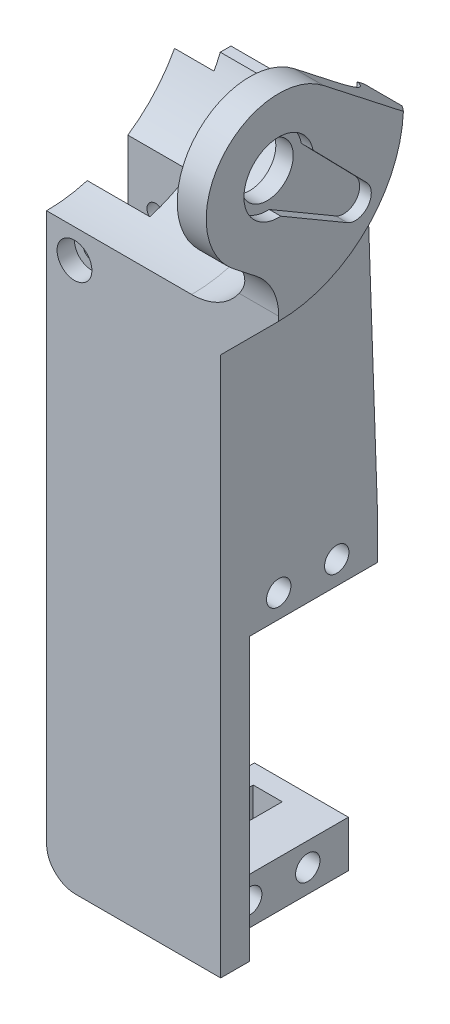
SolidWorks part; units mm, degrees
ref_plane "Alzado" through (0, 0, 0) normal (0, 0, 1) x (1, 0, 0)
ref_plane "Planta" through (0, 0, 0) normal (0, 1, 0) x (1, 0, 0)
ref_plane "Vista lateral" through (0, 0, 0) normal (1, 0, 0) x (0, 0, -1)
sketch "Croquis1" plane through (0, 0, 0) normal (0, 1, 0) x (1, 0, 0)
  line L1 (-15, -13.5) -> (15, -13.5)
  line L2 (-15, -13.5) -> (-15, 13.5)
  line L3 (-15, 13.5) -> (15, 13.5)
  line L4 (15, -13.5) -> (15, 13.5)
  line L5 (-15, -13.5) -> (15, 13.5) construction
  line L6 (-15, 13.5) -> (15, -13.5) construction
  point P0 (0, 0)
  dimension "D1" = 30
  dimension "D2" = 27
extrude "Saliente-Extruir1" add sketch "Croquis1" along normal blind 58.5 and the other way blind 56.5
sketch "Croquis17" plane through (0, 0, -13.5) normal (0, 0, -1) x (-1, 0, 0)
  line L1 (15, -48.5) -> (-15, -48.5)
  line L2 (15, -48.5) -> (15, -8)
  line L3 (15, -8) -> (-15, -8)
  line L4 (-15, -48.5) -> (-15, -8)
  line L5 (-15, -56.5) -> (-15, 58.5) construction
  line L6 (15, -56.5) -> (15, 58.5) construction
  dimension "D1" = 40.5
  dimension "D2" = 8
sketch "Croquis3" plane through (15, 0, 0) normal (1, 0, 0) x (0, 0, -1)
  line L0 (13.5, 0) -> (-13.5, 0) construction
  line L2 (-13.5, -56.5) -> (-13.5, 58.5) construction
  circle A0 centre (-13.5, 68) radius 31.5
  dimension "D1" = 63
  dimension "D2" = 68
extrude "Cortar-Extruir15" cut sketch "Croquis17" against normal blind 22
extrude "Saliente-Extruir2" add sketch "Croquis3" along normal blind 10
sketch "Croquis6" plane through (-15, 0, 0) normal (-1, 0, 0) x (0, 0, 1)
  line L0 (-13.5, 58.5) -> (13.5, 58.5) construction
  line L1 (-0.5, 58.5) -> (6.5, 58.5)
  line L2 (-0.5, 58.5) -> (-0.5, 33)
  line L3 (-0.5, 33) -> (6.5, 33)
  line L4 (6.5, 58.5) -> (6.5, 33)
  line L5 (13.5, -56.5) -> (13.5, 58.5) construction
  line L6 (22, 0) -> (-22, 0) construction
  dimension "D1" = 7
  dimension "D2" = 7
  dimension "D3" = 33
extrude "Cortar-Extruir5" cut sketch "Croquis6" against normal blind 10.8
sketch "Croquis8" plane through (15, 0, 0) normal (-1, 0, 0) x (0, 0, 1)
  line L2 (-11.2567, 64.5207) -> (-13.5, 0)
  line L5 (-13.5, -8) -> (-13.5, 51.775) construction
  line L8 (-11.2567, 64.5207) -> (5.8042, 77.8501)
  line L9 (21.1958, 58.1499) -> (13.5, 52.1373)
  line L10 (13.5, 36.5) -> (13.5, 58.5) construction
  line L11 (13.5, 52.1373) -> (13.5, 36.5)
  line L12 (21.725, 0) -> (-21.725, 0) construction
  line L13 (-13.5, 0) -> (-13.5, 51.775)
  arc A3 (21.1958, 58.1499) -> (5.8042, 77.8501) centre (13.5, 68) ccw
  circle A5 centre (13.5, 68) radius 25 construction
  arc A7 (13.5, 36.5) -> (-13.5, 51.775) centre (13.5, 68) ccw
  dimension "D1" = 25
  dimension "D2" = 128
  dimension "D5" = 50
  dimension "D3" = 31.5
extrude "Cortar-Extruir6" cut sketch "Croquis8" against normal through all and the other way up to surface (30 mm away) other way up to face at (-15, 6.1667, 0.1667)
sketch "Croquis5" plane through (-15, 0, 0) normal (-1, 0, 0) x (0, 0, 1)
  line L0 (-13.5, 0) -> (-11.466, 58.5)
  line L1 (-11.466, 58.5) -> (-8.4642, 58.5)
  line L2 (6.5, 58.5) -> (13.5, 58.5) construction
  line L3 (-8.4642, 58.5) -> (-10.4982, 0)
  line L4 (-10.4982, 0) -> (-13.5, 0)
  line L5 (21.725, 0) -> (-21.725, 0) construction
  line L6 (-13.5, 0) -> (-11.466, 58.5) construction
  dimension "D1" = 3
extrude "Cortar-Extruir4" cut sketch "Croquis5" against normal blind 6.8
sketch "Croquis9" plane through (-15, 0, 0) normal (-1, 0, 0) x (0, 0, 1)
  circle A0 centre (13.5, 68) radius 25
  dimension "D1" = 50
extrude "Cortar-Extruir7" cut sketch "Croquis9" against normal blind 35
sketch "Croquis10" plane through (25, 0, 0) normal (1, 0, 0) x (0, 0, -1)
  line L0 (-13.5, 68) -> (-0.3008, 57.6877) construction
  line L1 (11.2567, 64.5207) -> (-5.8042, 77.8501) construction
  line L2 (-13.1432, 62.0106) -> (-7.6022, 69.1027) construction
  line L3 (-7.6022, 69.1027) -> (1.6669, 59.6088)
  line L4 (-13.1432, 62.0106) -> (-1.6888, 55.3137)
  arc A0 (-7.6022, 69.1027) -> (-13.1432, 62.0106) centre (-13.5, 68) ccw
  arc A3 (-1.6888, 55.3137) -> (1.6669, 59.6088) centre (-0.3008, 57.6877) ccw
  point P10 (-10.3727, 65.5567)
  dimension "D1" = 12
  dimension "D3" = 5.5
  dimension "D2" = 16.75
  dimension "D4" = 9
extrude "Cortar-Extruir8" cut sketch "Croquis10" against normal blind 2 contours A0 region at (25, 64.7957, 9.3987)
sketch "Croquis12" plane through (0, 0, 13.5) normal (0, 0, 1) x (1, 0, 0)
  line L0 (-15, 38) -> (-10.2, 38) construction
  line L1 (-15, -56.5) -> (-15, 43) construction
  circle A0 centre (-10.2, 38) radius 3
  dimension "D3" = 6
  dimension "D1" = 4.8
  dimension "D2" = 5
extrude "Cortar-Extruir10" cut sketch "Croquis12" against normal blind 3 contours A0
sketch "Croquis13" plane through (0, 0, 10.5) normal (0, 0, 1) x (1, 0, 0)
  circle A0 centre (-10.2, 38) radius 1.5
  dimension "D1" = 3
extrude "Cortar-Extruir11" cut sketch "Croquis13" against normal through all
sketch "Croquis15" plane through (0, -56.5, 0) normal (0, -1, 0) x (1, 0, 0)
  line L0 (-0.5, 3.5) -> (-0.5, 13.5) construction
  line L2 (-0.5, -6.5) -> (-0.5, 3.5) construction
  line L3 (-15, 13.5) -> (15, 13.5) construction
  line L4 (2, -10.1) -> (-3, -10.1)
  line L5 (2, -10.1) -> (2, -2.9)
  line L6 (2, -2.9) -> (-3, -2.9)
  line L7 (-3, -10.1) -> (-3, -2.9)
  line L8 (2, -10.1) -> (-3, -2.9) construction
  line L9 (2, -2.9) -> (-3, -10.1) construction
  line L10 (2, -0.1) -> (-3, -0.1)
  line L11 (2, -0.1) -> (2, 7.1)
  line L12 (2, 7.1) -> (-3, 7.1)
  line L13 (-3, -0.1) -> (-3, 7.1)
  line L14 (2, -0.1) -> (-3, 7.1) construction
  line L15 (2, 7.1) -> (-3, -0.1) construction
  point P0 (0, 13.5)
  dimension "D1" = 10
  dimension "D2" = 0.5
  dimension "D3" = 10
  dimension "D4" = 7.2
  dimension "D5" = 5
extrude "Cortar-Extruir13" cut sketch "Croquis15" against normal up to vertex (56.5 mm away) up to point (-15, 0, -13.5)
sketch "Croquis19" plane through (15, 0, 0) normal (1, 0, 0) x (0, 0, -1)
  line L0 (-13.5, -52.5) -> (-3.5, -52.5) construction
  line L1 (-13.5, -56.5) -> (-13.5, 36.5) construction
  line L2 (13.5, -56.5) -> (13.5, -48.5) construction
  line L3 (-8.5, -28.25) -> (-13.5, -28.25) construction
  line L4 (-8.5, -8) -> (-8.5, -48.5) construction
  circle A0 centre (-3.5, -52.5) radius 2.1
  circle A1 centre (6.5, -52.5) radius 2.1
  circle A2 centre (6.5, -4) radius 2.1
  circle A3 centre (-3.5, -4) radius 2.1
  point P7 (13.5, -52.5)
  dimension "D2" = 4.2
  dimension "D1" = 10
  dimension "D3" = 10
extrude "Cortar-Extruir17" cut sketch "Croquis19" against normal blind 13
sketch "Croquis11" plane through (23, 0, 0) normal (1, 0, 0) x (0, 0, -1)
  circle A0 centre (-13.5, 68) radius 4.5
  dimension "D1" = 9
extrude "Cortar-Extruir9" cut sketch "Croquis11" against normal up to surface (3 mm away) up to face at (20, 59.7451, 9.7141)
sketch "Croquis20" plane through (0, -48.5, 0) normal (0, 1, 0) x (1, 0, 0)
  line L0 (15, -8.5) -> (-15, -8.5) construction
  line L1 (15, 13.5) -> (10, 13.5)
  line L2 (15, 13.5) -> (15, -8.5)
  line L3 (15, -8.5) -> (10, -8.5)
  line L4 (10, 13.5) -> (10, -8.5)
  line L6 (-15, 13.5) -> (-6.2, 13.5)
  line L7 (-15, 13.5) -> (-15, -8.5)
  line L8 (-15, -8.5) -> (-6.2, -8.5)
  line L9 (-6.2, 13.5) -> (-6.2, -8.5)
  dimension "D1" = 5
  dimension "D2" = 8.8
extrude "Cortar-Extruir18" cut sketch "Croquis20" against normal through all
fillet "Redondeo11" radius 5 1 edges at (-6.2, -52.5, 8.5)
fillet "Redondeo12" radius 5 1 edges at (-15, -56.5, 11)
fillet "Redondeo14" radius 3 1 edges at (-11.6, 0, -10.4982)
fillet "Redondeo1" radius 5 1 edges at (15, 58.5, -10.5453)
fillet "Redondeo9" radius 10 1 edges at (22.5, 52.1373, 13.5)
fillet "Redondeo8" radius 10 1 edges at (20, 49.1323, -2.9015)
chamfer "Chaflán1" distance 10 1 edges at (25, 39.8588, -0.6535)
